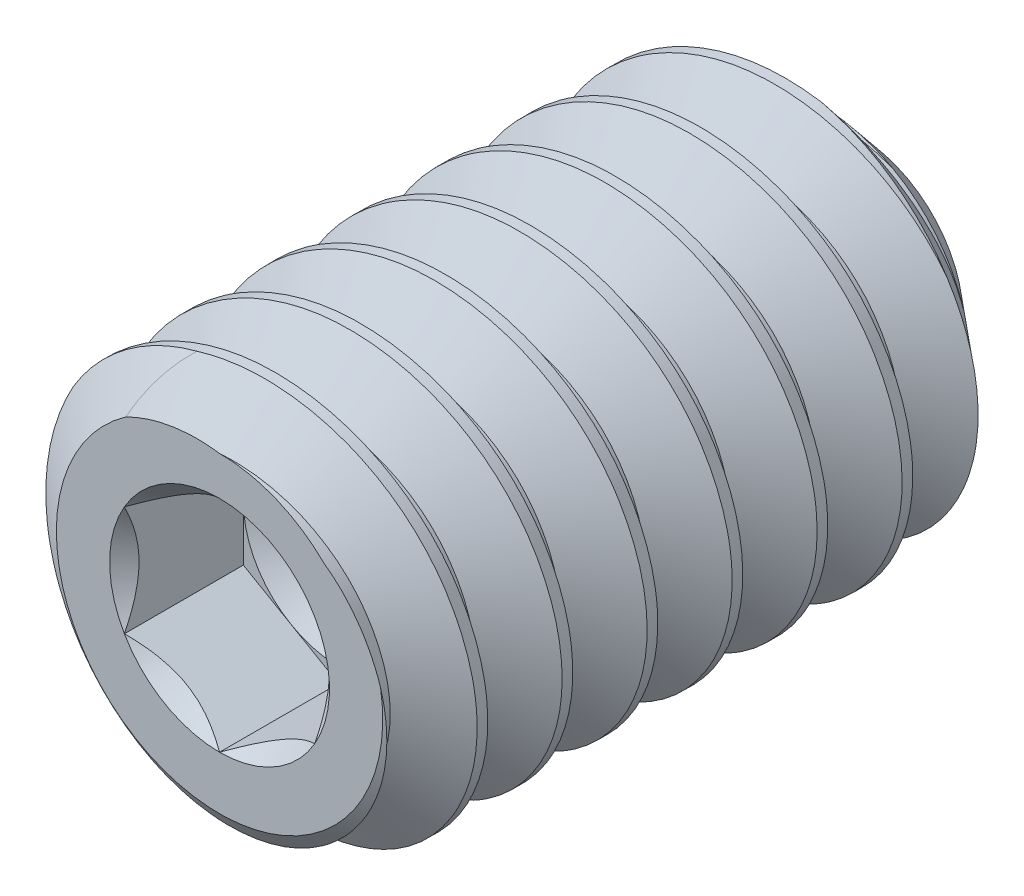
SolidWorks part; units mm, degrees
ref_plane "Front" through (0, 0, 0) normal (0, 0, 1) x (1, 0, 0)
ref_plane "Top" through (0, 0, 0) normal (0, 1, 0) x (1, 0, 0)
ref_plane "Right" through (0, 0, 0) normal (1, 0, 0) x (0, 0, -1)
sketch "Sketch22" plane through (0, 0, 0) normal (1, 0, 0) x (0, 0, -1)
  line L0 (-1.5875, 0) -> (-1.5875, 0.6096)
  line L1 (-1.5875, 0.6096) -> (-1.4808, 0.762) construction
  line L2 (-1.4808, 0.762) -> (0.4874, 0.762)
  line L3 (0.4874, 0.762) -> (0.7938, 0.3969) construction
  line L4 (-1.5875, 0.6096) -> (-1.5875, -0.6096) construction
  line L5 (1.5875, 0) -> (-1.5875, 0)
  line L6 (0, 0.762) -> (0, -0.762) construction
  line L8 (0.7938, 0.3969) -> (1.5875, 0.3969)
  line L9 (-0.9841, -0.762) -> (0.9841, -0.762) construction
  line L10 (1.5875, 0.3969) -> (1.5875, 0)
  line L11 (1.5875, 0.3969) -> (1.5875, -0.3969) construction
  line L12 (0.4874, 0.762) -> (0.7938, 0.762)
  line L13 (0.7938, 0.762) -> (0.7938, 0.3969)
  line L14 (-1.5875, 0.6096) -> (-1.5875, 0.762)
  line L15 (-1.5875, 0.762) -> (-1.4808, 0.762)
  dimension "D3" = 35
  dimension "D1" = 50
  dimension "D2" = 1.2192
revolve "Revolve1" add sketch "Sketch22" angle 360 about L5
ref_plane "Plane1" through (0, 0, -0.7938) normal (0, 0, 1) x (1, 0, 0)
sketch "Sketch27" plane through (0, 0, -0.7938) normal (0, 0, 1) x (1, 0, 0)
  circle A1 centre (0, 0) radius 0.762
  circle A5 centre (0, 0) radius 0.762 construction
curve "Helix/Spiral1" pitch 0.3175 height 2.8575 radius 0.762 centre (0, 0, -0.7938) axis (0, 0, 1) start towards (0, 1, 0)
sketch "Sketch28" plane through (0, 0, 0) normal (1, 0, 0) x (0, 0, -1)
  line L0 (0.7938, 0.762) -> (0.7938, -0.762) construction
  line L1 (0.7838, 0.7792) -> (1.0815, 0.7792)
  line L2 (0.7838, 0.7792) -> (0.9128, 0.5558)
  line L3 (0.9128, 0.5558) -> (0.9525, 0.5558)
  line L4 (1.0815, 0.7792) -> (0.9525, 0.5558)
  line L5 (0.7739, 0.7964) -> (1.0914, 0.7964) construction
  line L8 (0.7739, 0.7964) -> (0.9327, 0.5214) construction
  line L9 (0.9327, 0.5214) -> (1.0914, 0.7964) construction
  line L10 (0.9327, 0.7964) -> (0.9327, 0.762) construction
  line L11 (0.9327, 0.5214) -> (0.9327, 0.5558) construction
  line L12 (0.7938, 0.762) -> (1.0716, 0.762) construction
  line L13 (0.9128, 0.5558) -> (0.9525, 0.5558) construction
  line L14 (0.9327, 0.7792) -> (1.0815, 0.7792) construction
  dimension "D4" = 0.3175
  dimension "D5" = 0.0397
sweep "Cut-Sweep2" cut profiles "Sketch28" path "Helix/Spiral1" align with end faces yes
sketch "Sketch31" plane through (0, 0, 0) normal (1, 0, 0) x (0, 0, -1)
  line L0 (0.7938, 0.762) -> (0.7938, 0.3969) construction
  line L1 (0.4874, 0.762) -> (0.7938, 0.762) construction
  line L2 (0.4874, 0.762) -> (0.7938, 0.3969) construction
  line L3 (0.7938, 0.762) -> (0.7938, 0.3969)
  line L4 (0.4874, 0.762) -> (0.7938, 0.762)
  line L5 (0.4874, 0.762) -> (0.7938, 0.3969)
  line L6 (-1.5875, 0.6096) -> (-1.4808, 0.762) construction
  line L7 (-1.5875, 0.762) -> (-1.4808, 0.762) construction
  line L8 (-1.5875, 0.6096) -> (-1.5875, 0.762) construction
  line L9 (-1.5875, 0.762) -> (-1.4808, 0.762)
  line L10 (-1.5875, 0.6096) -> (-1.5875, 0.762)
  line L11 (-1.5875, 0.6096) -> (-1.4808, 0.762)
revolve "Cut-Revolve1" cut sketch "Sketch31" angle 360 about L5
sketch "Sketch23" plane through (0, 0, 1.5875) normal (0, 0, 1) x (1, 0, 0)
  line L1 (0, 0.4106) -> (-0.3556, 0.2053)
  line L2 (-0.3556, 0.2053) -> (-0.3556, -0.2053)
  line L3 (-0.3556, -0.2053) -> (0, -0.4106)
  line L4 (0, -0.4106) -> (0.3556, -0.2053)
  line L5 (0.3556, -0.2053) -> (0.3556, 0.2053)
  line L6 (0.3556, 0.2053) -> (0, 0.4106)
  circle A0 centre (0, 0) radius 0.3556 construction
  dimension "Hex" = 0.7112
extrude "Cut-Extrude10" cut sketch "Sketch23" against normal blind 0.4445
sketch "Sketch24" plane through (0, 0, 1.5875) normal (0, 0, 1) x (1, 0, 0)
  circle A0 centre (0, 0) radius 0.4106
extrude "Cut-Extrude11" cut sketch "Sketch24" against normal through all draft 45
sketch "Sketch26" plane through (0, 0, 1.143) normal (0, 0, 1) x (1, 0, 0)
  circle A0 centre (0, 0) radius 0.3556 construction
  circle A1 centre (0, 0) radius 0.3556
extrude "Cut-Extrude12" cut sketch "Sketch26" against normal through all draft 60
sketch "Sketch30" plane through (0, 0, 0) normal (1, 0, 0) x (0, 0, -1)
  line L0 (-1.4808, 0.762) -> (0.4874, 0.762) construction
  line L1 (-1.5875, 0) -> (-1.5875, 0.6096) construction
  line L2 (0.7938, 0.762) -> (0.7938, -0.762) construction
  line L3 (-0.9841, -0.762) -> (0.9841, -0.762) construction
  point P0 (-1.5875, 0.762)
  point P1 (1.5875, 0.762)
  point P2 (1.5875, -0.762)
  point P11 (-0.3175, -0.762)
  dimension "D1" = 1.1113
sketch "Sketch35" plane through (0, 0, -1.5875) normal (0, 0, -1) x (-1, 0, 0)
  circle A0 centre (0, 0) radius 0.3969
extrude "Cut-Extrude14" cut sketch "Sketch35" against normal blind 0.7937
equation "\"D3@Helix/Spiral1\"=\"Length@Sketch22\"*1.2"
equation "\"D1@Sketch30\" = \"D4@Helix/Spiral1\" * 3.5"
equation "\"hex Depth@Cut-Extrude10\" = \"Hex@Sketch23\" * .625"
equation "\"D2@Sketch22\" = \"Dia@Sketch22\" * .8"
equation "\"D5@Sketch28\"=\"D4@Helix/Spiral1\"*.125"
equation "\"D4@Sketch28\"=\"D4@Helix/Spiral1\""
